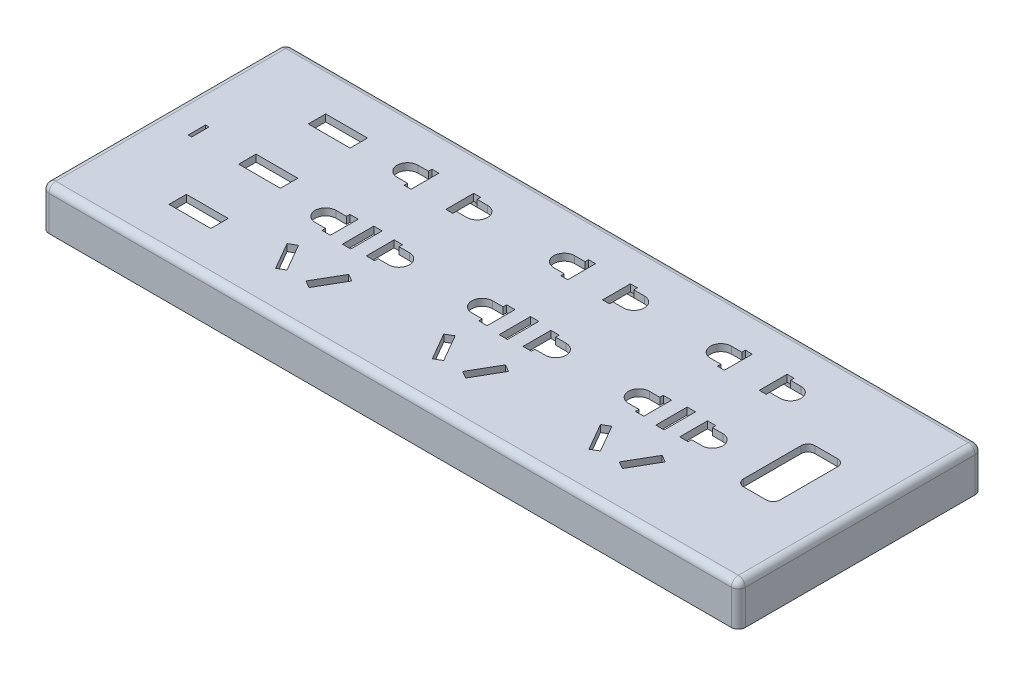
SolidWorks part; units mm, degrees
material "ABS"
ref_plane "前视基准面" through (0, 0, 0) normal (0, 0, 1) x (1, 0, 0)
ref_plane "上视基准面" through (0, 0, 0) normal (0, 1, 0) x (1, 0, 0)
ref_plane "右视基准面" through (0, 0, 0) normal (1, 0, 0) x (0, 0, -1)
ref_plane "BoxInnerTop" through (0, 0, 0) normal (0, 1, 0) x (1, 0, 0)
ref_plane "ConnectFace" through (0, -10, 0) normal (0, 1, 0) x (1, 0, 0)
sketch "SketchRec" plane through (0, 0, 0) normal (0, 1, 0) x (1, 0, 0)
  line L1 (-100, -35) -> (100, -35)
  line L2 (-100, -35) -> (-100, 35)
  line L3 (-100, 35) -> (100, 35)
  line L4 (100, -35) -> (100, 35)
  line L5 (-100, -35) -> (100, 35) construction
  line L6 (-100, 35) -> (100, -35) construction
  point P0 (0, 0)
  dimension "L" = 200
  dimension "KD" = 70
extrude "RectangleBox" add sketch "SketchRec" along normal blind 2 and the other way blind 10
fillet "RectangleR" radius 2 8 edges at (-100, -4, 35) (-100, -4, -35) (100, -4, -35) (100, -4, 35) (100, 2, 0) (0, 2, -35) (-100, 2, 0) (0, 2, 35)
shell "RectangleC" thickness 2 removed face at (0, -10, 0)
sketch "SketchCircle" [suppressed] plane through (0, 0, 0) normal (0, 1, 0) x (1, 0, 0)
  circle A0 centre (0, 0) radius 80
  dimension "D1" = 160
extrude "CircleBox" [suppressed] add sketch "SketchCircle" along normal blind 2 and the other way blind 10 contours A0
fillet "CircleR" [suppressed] radius 2
shell "CircleC" [suppressed] thickness 2
sketch "SButtonCut" plane through (0, -10, 0) normal (0, 1, 0) x (1, 0, 0)
  line L4 (83.25, 10.25) -> (76.75, 10.25)
  line L5 (85.25, -8.25) -> (85.25, 8.25)
  line L6 (76.75, -10.25) -> (83.25, -10.25)
  line L7 (74.75, 8.25) -> (74.75, -8.25)
  line L8 (83.25, 10.25) -> (76.75, 10.25)
  line L9 (85.25, -8.25) -> (85.25, 8.25)
  line L10 (76.75, -10.25) -> (83.25, -10.25)
  line L11 (74.75, 8.25) -> (74.75, -8.25)
  arc A4 (85.25, 8.25) -> (83.25, 10.25) centre (83.25, 8.25) ccw
  arc A5 (83.25, -10.25) -> (85.25, -8.25) centre (83.25, -8.25) ccw
  arc A6 (74.75, -8.25) -> (76.75, -10.25) centre (76.75, -8.25) ccw
  arc A7 (76.75, 10.25) -> (74.75, 8.25) centre (76.75, 8.25) ccw
  arc A8 (85.25, 8.25) -> (83.25, 10.25) centre (83.25, 8.25) ccw
  arc A9 (83.25, -10.25) -> (85.25, -8.25) centre (83.25, -8.25) ccw
  arc A10 (74.75, -8.25) -> (76.75, -10.25) centre (76.75, -8.25) ccw
  arc A11 (76.75, 10.25) -> (74.75, 8.25) centre (76.75, 8.25) ccw
  dimension "D1" = 0
extrude "FButtonCut" cut sketch "SButtonCut" along normal through all
sketch "SLEDCut" plane through (0, -10, 0) normal (0, 1, 0) x (1, 0, 0)
  line L4 (-90.5, -2.5) -> (-89.5, -2.5)
  line L5 (-89.5, -2.5) -> (-89.5, 2.5)
  line L6 (-89.5, 2.5) -> (-90.5, 2.5)
  line L7 (-90.5, 2.5) -> (-90.5, -2.5)
  line L8 (-90.5, -2.5) -> (-89.5, -2.5)
  line L9 (-89.5, -2.5) -> (-89.5, 2.5)
  line L10 (-89.5, 2.5) -> (-90.5, 2.5)
  line L11 (-90.5, 2.5) -> (-90.5, -2.5)
  dimension "D1" = 0
extrude "FLEDCut" cut sketch "SLEDCut" along normal through all
sketch "SSlotA" plane through (0, -10, 0) normal (0, 1, 0) x (1, 0, 0)
  line L4 (-38.8, 1.5) -> (-41.2, 1.5)
  line L5 (-38.8, -7.5) -> (-38.8, 1.5)
  line L6 (-41.2, -7.5) -> (-38.8, -7.5)
  line L7 (-45.15, -7) -> (-45.15, 1)
  line L8 (-47.55, -7) -> (-45.15, -7)
  line L9 (-47.55, -6) -> (-47.55, -7)
  line L10 (-50.55, -6) -> (-47.55, -6)
  line L11 (-47.55, 0) -> (-50.55, 0)
  line L12 (-47.55, 1) -> (-47.55, 0)
  line L13 (-45.15, 1) -> (-47.55, 1)
  line L14 (-45.15, -7) -> (-45.15, 1)
  line L15 (-47.55, -7) -> (-45.15, -7)
  line L16 (-47.55, -6) -> (-47.55, -7)
  line L17 (-50.55, -6) -> (-47.55, -6)
  line L18 (-47.55, 0) -> (-50.55, 0)
  line L19 (-47.55, 1) -> (-47.55, 0)
  line L20 (-45.15, 1) -> (-47.55, 1)
  line L21 (-41.2, 1.5) -> (-41.2, -7.5)
  line L22 (-38.8, 1.5) -> (-41.2, 1.5)
  line L23 (-38.8, -7.5) -> (-38.8, 1.5)
  line L24 (-41.2, -7.5) -> (-38.8, -7.5)
  line L25 (-41.2, 1.5) -> (-41.2, -7.5)
  line L26 (-37.2831, -21.8942) -> (-35.2047, -23.0942)
  line L27 (-35.2047, -23.0942) -> (-30.7047, -15.3)
  line L28 (-30.7047, -15.3) -> (-32.7831, -14.1)
  line L29 (-32.45, 0) -> (-32.45, 1)
  line L30 (-29.45, 0) -> (-32.45, 0)
  line L31 (-32.45, -6) -> (-29.45, -6)
  line L32 (-32.45, -7) -> (-32.45, -6)
  line L33 (-34.85, -7) -> (-32.45, -7)
  line L34 (-34.85, 1) -> (-34.85, -7)
  line L35 (-32.45, 1) -> (-34.85, 1)
  line L36 (-32.45, 0) -> (-32.45, 1)
  line L37 (-29.45, 0) -> (-32.45, 0)
  line L38 (-32.45, -6) -> (-29.45, -6)
  line L39 (-32.45, -7) -> (-32.45, -6)
  line L40 (-34.85, -7) -> (-32.45, -7)
  line L41 (-34.85, 1) -> (-34.85, -7)
  line L42 (-32.45, 1) -> (-34.85, 1)
  line L43 (-32.7831, -14.1) -> (-37.2831, -21.8942)
  line L44 (-37.2831, -21.8942) -> (-35.2047, -23.0942)
  line L45 (-35.2047, -23.0942) -> (-30.7047, -15.3)
  line L46 (-30.7047, -15.3) -> (-32.7831, -14.1)
  line L47 (-32.7831, -14.1) -> (-37.2831, -21.8942)
  line L48 (-49.2953, -15.3) -> (-44.7953, -23.0942)
  line L49 (-47.2169, -14.1) -> (-49.2953, -15.3)
  line L50 (-42.7169, -21.8942) -> (-47.2169, -14.1)
  line L51 (-44.7953, -23.0942) -> (-42.7169, -21.8942)
  line L52 (-49.2953, -15.3) -> (-44.7953, -23.0942)
  line L53 (-47.2169, -14.1) -> (-49.2953, -15.3)
  line L54 (-42.7169, -21.8942) -> (-47.2169, -14.1)
  line L55 (-44.7953, -23.0942) -> (-42.7169, -21.8942)
  arc A1 (-50.55, 0) -> (-50.55, -6) centre (-50.55, -3) ccw
  arc A2 (-50.55, 0) -> (-50.55, -6) centre (-50.55, -3) ccw
  arc A3 (-29.45, -6) -> (-29.45, 0) centre (-29.45, -3) ccw
  arc A4 (-29.45, -6) -> (-29.45, 0) centre (-29.45, -3) ccw
  dimension "D1" = 0
  dimension "D2" = 0
  dimension "D3" = 0
  dimension "D4" = 0
  dimension "D5" = 0
extrude "FSlotACut" cut sketch "SSlotA" along normal through all
sketch "SSlotA2" plane through (0, -10, 0) normal (0, 1, 0) x (1, 0, 0)
  line L4 (6.2, 1.5) -> (3.8, 1.5)
  line L5 (6.2, -7.5) -> (6.2, 1.5)
  line L6 (3.8, -7.5) -> (6.2, -7.5)
  line L7 (-0.15, -7) -> (-0.15, 1)
  line L8 (-2.55, -7) -> (-0.15, -7)
  line L9 (-2.55, -6) -> (-2.55, -7)
  line L10 (-5.55, -6) -> (-2.55, -6)
  line L11 (-2.55, 0) -> (-5.55, 0)
  line L12 (-2.55, 1) -> (-2.55, 0)
  line L13 (-0.15, 1) -> (-2.55, 1)
  line L14 (-0.15, -7) -> (-0.15, 1)
  line L15 (-2.55, -7) -> (-0.15, -7)
  line L16 (-2.55, -6) -> (-2.55, -7)
  line L17 (-5.55, -6) -> (-2.55, -6)
  line L18 (-2.55, 0) -> (-5.55, 0)
  line L19 (-2.55, 1) -> (-2.55, 0)
  line L20 (-0.15, 1) -> (-2.55, 1)
  line L21 (3.8, 1.5) -> (3.8, -7.5)
  line L22 (6.2, 1.5) -> (3.8, 1.5)
  line L23 (6.2, -7.5) -> (6.2, 1.5)
  line L24 (3.8, -7.5) -> (6.2, -7.5)
  line L25 (3.8, 1.5) -> (3.8, -7.5)
  line L26 (7.7169, -21.8942) -> (9.7953, -23.0942)
  line L27 (9.7953, -23.0942) -> (14.2953, -15.3)
  line L28 (14.2953, -15.3) -> (12.2169, -14.1)
  line L29 (12.55, 0) -> (12.55, 1)
  line L30 (15.55, 0) -> (12.55, 0)
  line L31 (12.55, -6) -> (15.55, -6)
  line L32 (12.55, -7) -> (12.55, -6)
  line L33 (10.15, -7) -> (12.55, -7)
  line L34 (10.15, 1) -> (10.15, -7)
  line L35 (12.55, 1) -> (10.15, 1)
  line L36 (12.55, 0) -> (12.55, 1)
  line L37 (15.55, 0) -> (12.55, 0)
  line L38 (12.55, -6) -> (15.55, -6)
  line L39 (12.55, -7) -> (12.55, -6)
  line L40 (10.15, -7) -> (12.55, -7)
  line L41 (10.15, 1) -> (10.15, -7)
  line L42 (12.55, 1) -> (10.15, 1)
  line L43 (12.2169, -14.1) -> (7.7169, -21.8942)
  line L44 (7.7169, -21.8942) -> (9.7953, -23.0942)
  line L45 (9.7953, -23.0942) -> (14.2953, -15.3)
  line L46 (14.2953, -15.3) -> (12.2169, -14.1)
  line L47 (12.2169, -14.1) -> (7.7169, -21.8942)
  line L48 (-4.2953, -15.3) -> (0.2047, -23.0942)
  line L49 (-2.2169, -14.1) -> (-4.2953, -15.3)
  line L50 (2.2831, -21.8942) -> (-2.2169, -14.1)
  line L51 (0.2047, -23.0942) -> (2.2831, -21.8942)
  line L52 (-4.2953, -15.3) -> (0.2047, -23.0942)
  line L53 (-2.2169, -14.1) -> (-4.2953, -15.3)
  line L54 (2.2831, -21.8942) -> (-2.2169, -14.1)
  line L55 (0.2047, -23.0942) -> (2.2831, -21.8942)
  arc A1 (-5.55, 0) -> (-5.55, -6) centre (-5.55, -3) ccw
  arc A2 (-5.55, 0) -> (-5.55, -6) centre (-5.55, -3) ccw
  arc A3 (15.55, -6) -> (15.55, 0) centre (15.55, -3) ccw
  arc A4 (15.55, -6) -> (15.55, 0) centre (15.55, -3) ccw
  dimension "D1" = 0
  dimension "D2" = 0
  dimension "D3" = 0
  dimension "D4" = 0
  dimension "D5" = 0
extrude "FSlotA2Cut" cut sketch "SSlotA2" along normal through all
sketch "SSlotA3" plane through (0, -10, 0) normal (0, 1, 0) x (1, 0, 0)
  line L4 (51.2, 1.5) -> (48.8, 1.5)
  line L5 (51.2, -7.5) -> (51.2, 1.5)
  line L6 (48.8, -7.5) -> (51.2, -7.5)
  line L7 (44.85, -7) -> (44.85, 1)
  line L8 (42.45, -7) -> (44.85, -7)
  line L9 (42.45, -6) -> (42.45, -7)
  line L10 (39.45, -6) -> (42.45, -6)
  line L11 (42.45, 0) -> (39.45, 0)
  line L12 (42.45, 1) -> (42.45, 0)
  line L13 (44.85, 1) -> (42.45, 1)
  line L14 (44.85, -7) -> (44.85, 1)
  line L15 (42.45, -7) -> (44.85, -7)
  line L16 (42.45, -6) -> (42.45, -7)
  line L17 (39.45, -6) -> (42.45, -6)
  line L18 (42.45, 0) -> (39.45, 0)
  line L19 (42.45, 1) -> (42.45, 0)
  line L20 (44.85, 1) -> (42.45, 1)
  line L21 (48.8, 1.5) -> (48.8, -7.5)
  line L22 (51.2, 1.5) -> (48.8, 1.5)
  line L23 (51.2, -7.5) -> (51.2, 1.5)
  line L24 (48.8, -7.5) -> (51.2, -7.5)
  line L25 (48.8, 1.5) -> (48.8, -7.5)
  line L26 (52.7169, -21.8942) -> (54.7953, -23.0942)
  line L27 (54.7953, -23.0942) -> (59.2953, -15.3)
  line L28 (59.2953, -15.3) -> (57.2169, -14.1)
  line L29 (57.55, 0) -> (57.55, 1)
  line L30 (60.55, 0) -> (57.55, 0)
  line L31 (57.55, -6) -> (60.55, -6)
  line L32 (57.55, -7) -> (57.55, -6)
  line L33 (55.15, -7) -> (57.55, -7)
  line L34 (55.15, 1) -> (55.15, -7)
  line L35 (57.55, 1) -> (55.15, 1)
  line L36 (57.55, 0) -> (57.55, 1)
  line L37 (60.55, 0) -> (57.55, 0)
  line L38 (57.55, -6) -> (60.55, -6)
  line L39 (57.55, -7) -> (57.55, -6)
  line L40 (55.15, -7) -> (57.55, -7)
  line L41 (55.15, 1) -> (55.15, -7)
  line L42 (57.55, 1) -> (55.15, 1)
  line L43 (57.2169, -14.1) -> (52.7169, -21.8942)
  line L44 (52.7169, -21.8942) -> (54.7953, -23.0942)
  line L45 (54.7953, -23.0942) -> (59.2953, -15.3)
  line L46 (59.2953, -15.3) -> (57.2169, -14.1)
  line L47 (57.2169, -14.1) -> (52.7169, -21.8942)
  line L48 (40.7047, -15.3) -> (45.2047, -23.0942)
  line L49 (42.7831, -14.1) -> (40.7047, -15.3)
  line L50 (47.2831, -21.8942) -> (42.7831, -14.1)
  line L51 (45.2047, -23.0942) -> (47.2831, -21.8942)
  line L52 (40.7047, -15.3) -> (45.2047, -23.0942)
  line L53 (42.7831, -14.1) -> (40.7047, -15.3)
  line L54 (47.2831, -21.8942) -> (42.7831, -14.1)
  line L55 (45.2047, -23.0942) -> (47.2831, -21.8942)
  arc A1 (39.45, 0) -> (39.45, -6) centre (39.45, -3) ccw
  arc A2 (39.45, 0) -> (39.45, -6) centre (39.45, -3) ccw
  arc A3 (60.55, -6) -> (60.55, 0) centre (60.55, -3) ccw
  arc A4 (60.55, -6) -> (60.55, 0) centre (60.55, -3) ccw
  dimension "D1" = 0
  dimension "D2" = 0
  dimension "D3" = 0
  dimension "D4" = 0
  dimension "D5" = 0
extrude "FSlotA3Cut" cut sketch "SSlotA3" along normal through all
sketch "SSlotB" plane through (0, -10, 0) normal (0, 1, 0) x (1, 0, 0)
  line L7 (-45, 16) -> (-45, 24)
  line L8 (-47, 16) -> (-45, 16)
  line L9 (-47, 17) -> (-47, 16)
  line L10 (-50, 17) -> (-47, 17)
  line L11 (-47, 23) -> (-50, 23)
  line L12 (-47, 24) -> (-47, 23)
  line L13 (-45, 24) -> (-47, 24)
  line L14 (-45, 16) -> (-45, 24)
  line L15 (-47, 16) -> (-45, 16)
  line L16 (-47, 17) -> (-47, 16)
  line L17 (-50, 17) -> (-47, 17)
  line L18 (-47, 23) -> (-50, 23)
  line L19 (-47, 24) -> (-47, 23)
  line L20 (-45, 24) -> (-47, 24)
  line L21 (-33, 17) -> (-30, 17)
  line L22 (-30, 23) -> (-33, 23)
  line L23 (-33, 23) -> (-33, 24)
  line L24 (-33, 24) -> (-35, 24)
  line L25 (-35, 24) -> (-35, 16)
  line L26 (-35, 16) -> (-33, 16)
  line L27 (-33, 16) -> (-33, 17)
  line L28 (-33, 17) -> (-30, 17)
  line L29 (-30, 23) -> (-33, 23)
  line L30 (-33, 23) -> (-33, 24)
  line L31 (-33, 24) -> (-35, 24)
  line L32 (-35, 24) -> (-35, 16)
  line L33 (-35, 16) -> (-33, 16)
  line L34 (-33, 16) -> (-33, 17)
  arc A1 (-50, 23) -> (-50, 17) centre (-50, 20) ccw
  arc A2 (-50, 23) -> (-50, 17) centre (-50, 20) ccw
  arc A3 (-30, 17) -> (-30, 23) centre (-30, 20) ccw
  arc A4 (-30, 17) -> (-30, 23) centre (-30, 20) ccw
  dimension "D1" = 0
  dimension "D2" = 0
extrude "FSlotBCut" cut sketch "SSlotB" along normal through all
sketch "SSlotB2" plane through (0, -10, 0) normal (0, 1, 0) x (1, 0, 0)
  line L7 (0, 16) -> (0, 24)
  line L8 (-2, 16) -> (0, 16)
  line L9 (-2, 17) -> (-2, 16)
  line L10 (-5, 17) -> (-2, 17)
  line L11 (-2, 23) -> (-5, 23)
  line L12 (-2, 24) -> (-2, 23)
  line L13 (0, 24) -> (-2, 24)
  line L14 (0, 16) -> (0, 24)
  line L15 (-2, 16) -> (0, 16)
  line L16 (-2, 17) -> (-2, 16)
  line L17 (-5, 17) -> (-2, 17)
  line L18 (-2, 23) -> (-5, 23)
  line L19 (-2, 24) -> (-2, 23)
  line L20 (0, 24) -> (-2, 24)
  line L21 (12, 17) -> (15, 17)
  line L22 (15, 23) -> (12, 23)
  line L23 (12, 23) -> (12, 24)
  line L24 (12, 24) -> (10, 24)
  line L25 (10, 24) -> (10, 16)
  line L26 (10, 16) -> (12, 16)
  line L27 (12, 16) -> (12, 17)
  line L28 (12, 17) -> (15, 17)
  line L29 (15, 23) -> (12, 23)
  line L30 (12, 23) -> (12, 24)
  line L31 (12, 24) -> (10, 24)
  line L32 (10, 24) -> (10, 16)
  line L33 (10, 16) -> (12, 16)
  line L34 (12, 16) -> (12, 17)
  arc A1 (-5, 23) -> (-5, 17) centre (-5, 20) ccw
  arc A2 (-5, 23) -> (-5, 17) centre (-5, 20) ccw
  arc A3 (15, 17) -> (15, 23) centre (15, 20) ccw
  arc A4 (15, 17) -> (15, 23) centre (15, 20) ccw
  dimension "D1" = 0
  dimension "D2" = 0
extrude "FSlotB2Cut" cut sketch "SSlotB2" along normal through all
sketch "SSlotB3" plane through (0, -10, 0) normal (0, 1, 0) x (1, 0, 0)
  line L7 (45, 16) -> (45, 24)
  line L8 (43, 16) -> (45, 16)
  line L9 (43, 17) -> (43, 16)
  line L10 (40, 17) -> (43, 17)
  line L11 (43, 23) -> (40, 23)
  line L12 (43, 24) -> (43, 23)
  line L13 (45, 24) -> (43, 24)
  line L14 (45, 16) -> (45, 24)
  line L15 (43, 16) -> (45, 16)
  line L16 (43, 17) -> (43, 16)
  line L17 (40, 17) -> (43, 17)
  line L18 (43, 23) -> (40, 23)
  line L19 (43, 24) -> (43, 23)
  line L20 (45, 24) -> (43, 24)
  line L21 (57, 17) -> (60, 17)
  line L22 (60, 23) -> (57, 23)
  line L23 (57, 23) -> (57, 24)
  line L24 (57, 24) -> (55, 24)
  line L25 (55, 24) -> (55, 16)
  line L26 (55, 16) -> (57, 16)
  line L27 (57, 16) -> (57, 17)
  line L28 (57, 17) -> (60, 17)
  line L29 (60, 23) -> (57, 23)
  line L30 (57, 23) -> (57, 24)
  line L31 (57, 24) -> (55, 24)
  line L32 (55, 24) -> (55, 16)
  line L33 (55, 16) -> (57, 16)
  line L34 (57, 16) -> (57, 17)
  arc A1 (40, 23) -> (40, 17) centre (40, 20) ccw
  arc A2 (40, 23) -> (40, 17) centre (40, 20) ccw
  arc A3 (60, 17) -> (60, 23) centre (60, 20) ccw
  arc A4 (60, 17) -> (60, 23) centre (60, 20) ccw
  dimension "D1" = 0
  dimension "D2" = 0
extrude "FSlotB3Cut" cut sketch "SSlotB3" along normal through all
sketch "SSlotC" plane through (0, -10, 0) normal (0, 1, 0) x (1, 0, 0)
  line L4 (-64, 17.5) -> (-64, 22.5)
  line L5 (-64, 22.5) -> (-76, 22.5)
  line L6 (-76, 22.5) -> (-76, 17.5)
  line L7 (-76, 17.5) -> (-64, 17.5)
  line L8 (-64, 17.5) -> (-64, 22.5)
  line L9 (-64, 22.5) -> (-76, 22.5)
  line L10 (-76, 22.5) -> (-76, 17.5)
  line L11 (-76, 17.5) -> (-64, 17.5)
  dimension "D1" = 0
extrude "FSlotCCut" cut sketch "SSlotC" along normal through all
sketch "SSlotC2" plane through (0, -10, 0) normal (0, 1, 0) x (1, 0, 0)
  line L4 (-64, -2.5) -> (-64, 2.5)
  line L5 (-64, 2.5) -> (-76, 2.5)
  line L6 (-76, 2.5) -> (-76, -2.5)
  line L7 (-76, -2.5) -> (-64, -2.5)
  line L8 (-64, -2.5) -> (-64, 2.5)
  line L9 (-64, 2.5) -> (-76, 2.5)
  line L10 (-76, 2.5) -> (-76, -2.5)
  line L11 (-76, -2.5) -> (-64, -2.5)
  dimension "D1" = 0
extrude "FSlotC2Cut" cut sketch "SSlotC2" along normal through all
sketch "SSlotC3" plane through (0, -10, 0) normal (0, 1, 0) x (1, 0, 0)
  line L4 (-64, -22.5) -> (-64, -17.5)
  line L5 (-64, -17.5) -> (-76, -17.5)
  line L6 (-76, -17.5) -> (-76, -22.5)
  line L7 (-76, -22.5) -> (-64, -22.5)
  line L8 (-64, -22.5) -> (-64, -17.5)
  line L9 (-64, -17.5) -> (-76, -17.5)
  line L10 (-76, -17.5) -> (-76, -22.5)
  line L11 (-76, -22.5) -> (-64, -22.5)
  dimension "D1" = 0
extrude "FSlotC3Cut" cut sketch "SSlotC3" along normal through all
equation "\"H\"= 10"
equation "\"Tn\"= 2"
equation "\"D1@RectangleBox\"=\"Tn\""
equation "\"D2@RectangleBox\"=\"H\""
equation "\"D1@CircleBox\"=\"Tn\""
equation "\"D2@CircleBox\"=\"H\""
equation "\"DisCt@ConnectFace\"=\"H\""
equation "\"D1@RectangleC\"=\"D1@RectangleR\""
